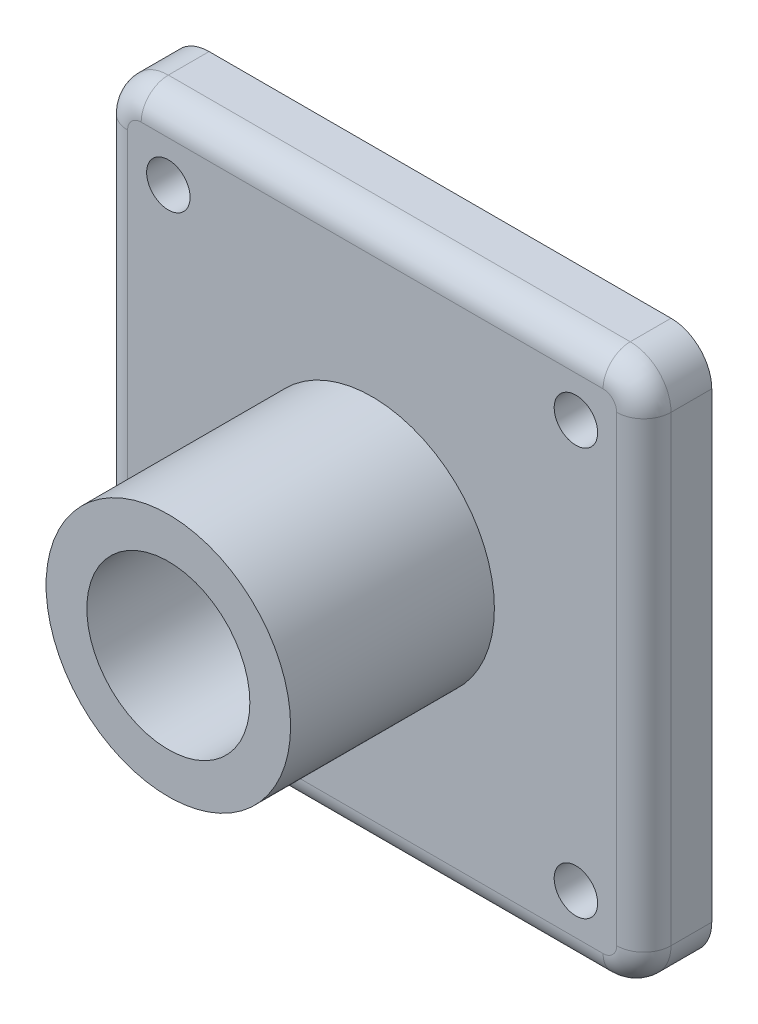
SolidWorks part; units mm, degrees
ref_plane "Front Plane" through (0, 0, 0) normal (0, 0, 1) x (1, 0, 0)
ref_plane "Top Plane" through (0, 0, 0) normal (0, 1, 0) x (1, 0, 0)
ref_plane "Right Plane" through (0, 0, 0) normal (1, 0, 0) x (0, 0, -1)
sketch "Sketch2" plane through (0, 0, 0) normal (0, 0, 1) x (1, 0, 0)
  circle A0 centre (-135, -82.3127) radius 6
  circle A1 centre (-135, -82.3127) radius 9
extrude "Boss-Extrude1" add sketch "Sketch2" along normal blind 20
sketch "Sketch3" plane through (0, 0, 0) normal (0, 0, -1) x (-1, 0, 0)
  line L1 (152, -102.3127) -> (118, -102.3127)
  line L2 (155, -99.3127) -> (155, -65.3127)
  line L3 (152, -62.3127) -> (118, -62.3127)
  line L4 (115, -99.3127) -> (115, -65.3127)
  circle A0 centre (135, -82.3127) radius 6
  arc A5 (118, -102.3127) -> (115, -99.3127) centre (118, -99.3127) cw
  arc A6 (152, -102.3127) -> (155, -99.3127) centre (152, -99.3127) ccw
  arc A7 (155, -65.3127) -> (152, -62.3127) centre (152, -65.3127) ccw
  arc A8 (118, -62.3127) -> (115, -65.3127) centre (118, -65.3127) ccw
  point P8 (115, -102.3127)
  point P11 (155, -102.3127)
  point P14 (155, -62.3127)
  dimension "D1" = 20
  dimension "D5" = 3
  dimension "D2" = 40
  dimension "D3" = 40
  dimension "D4" = 20
extrude "Boss-Extrude2" add sketch "Sketch3" against normal blind 5
fillet "Fillet1" radius 2 8 edges at (-154.1213, -101.434, 5) (-135, -102.3127, 5) (-115.8787, -101.434, 5) (-115, -82.3127, 5) (-115.8787, -63.1913, 5) (-135, -62.3127, 5) (-154.1213, -63.1913, 5) (-155, -82.3127, 5)
sketch "Sketch4" plane through (0, 0, 5) normal (0, 0, 1) x (1, 0, 0)
  line L2 (-135, -62.3127) -> (-135, -102.3127) construction
  line L3 (-152, -62.3127) -> (-118, -62.3127) construction
  line L4 (-118, -102.3127) -> (-152, -102.3127) construction
  line L5 (-155, -82.3127) -> (-115, -82.3127) construction
  line L6 (-155, -99.3127) -> (-155, -65.3127) construction
  line L7 (-115, -65.3127) -> (-115, -99.3127) construction
  circle A0 centre (-150, -67.3127) radius 1.6
  circle A1 centre (-120, -67.3127) radius 1.6
  circle A2 centre (-120, -97.3127) radius 1.6
  circle A3 centre (-150, -97.3127) radius 1.6
extrude "Cut-Extrude1" cut sketch "Sketch4" against normal up to surface (7 mm away)
